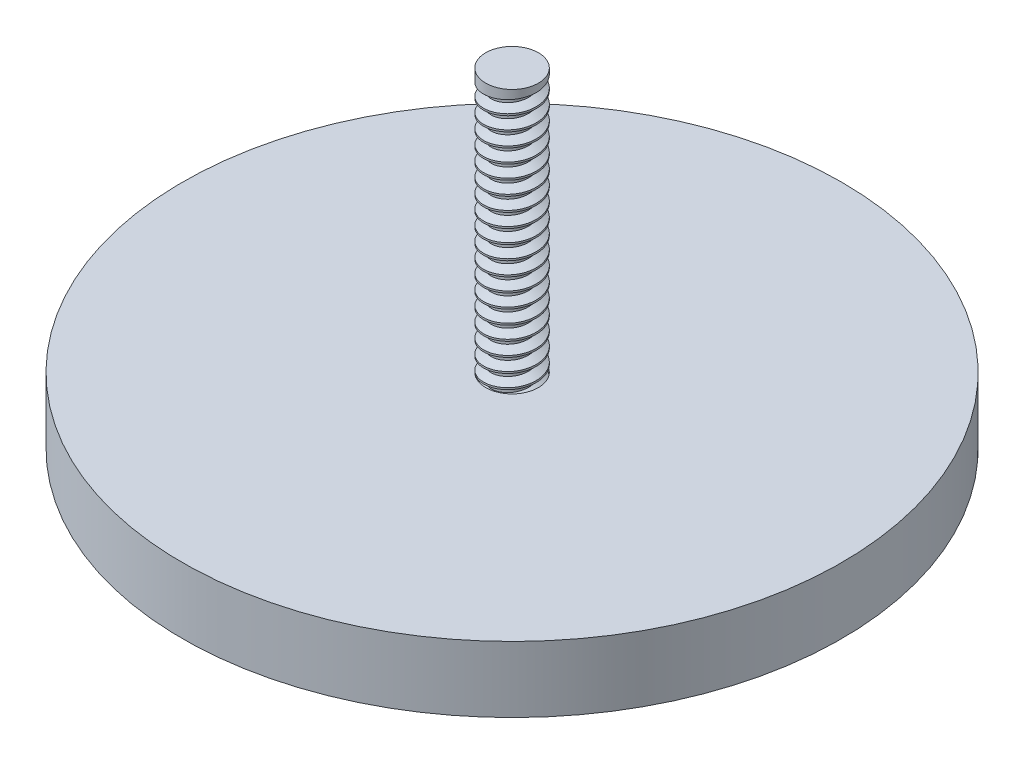
SolidWorks part; units mm, degrees
ref_plane "Front Plane" through (0, 0, 0) normal (0, 0, 1) x (1, 0, 0)
ref_plane "Top Plane" through (0, 0, 0) normal (0, 1, 0) x (1, 0, 0)
ref_plane "Right Plane" through (0, 0, 0) normal (1, 0, 0) x (0, 0, -1)
sketch "Sketch1" plane through (0, 0, 0) normal (0, 0, 1) x (1, 0, 0)
  line L1 (-25, 0) -> (0, 0)
  line L2 (-25, 0) -> (-25, 5)
  line L3 (-25, 5) -> (-2, 5)
  line L6 (0, 0) -> (0, 25)
  line L7 (0, 25) -> (-2, 25)
  line L8 (-2, 5) -> (-2, 25)
  point P1 (0, 0)
  point P7 (-8.3339, -1.6381)
  dimension "D1" = 5
  dimension "D2" = 25
  dimension "D3" = 25
  dimension "D4" = 2
revolve "Revolve1" add sketch "Sketch1" angle 360 about L6
thread "Thread1" pitch 1.0583 start angle 0, offset 0, length 0, pitch 1.0583, diameter 4
ref_plane "Plane1" through (-2, 25, 0) normal (0, 0, 1) x (-1, 0, 0)
sketch "Thread Profile1" plane through (-2, 25, 0) normal (0, 0, 1) x (-1, 0, 0)
  line L0 (0, 0) -> (0, 1.0583) construction
  line L11 (0, 0) -> (0, 0.926)
  line L12 (0, 0.926) -> (-0.5728, 0.5953)
  line L13 (-0.5728, 0.5953) -> (-0.5728, 0.3307)
  line L15 (-0.5728, 0.3307) -> (0, 0)
  line L17 (-0.5728, 0.463) -> (0, 0.463) construction
  point P2 (0, 0)
  dimension "Pitch" = 1.0583
  dimension "Profile_Angle" = 60
  dimension "Profile_Land" = 0.2646
  dimension "Profile_Height" = 0.5728
